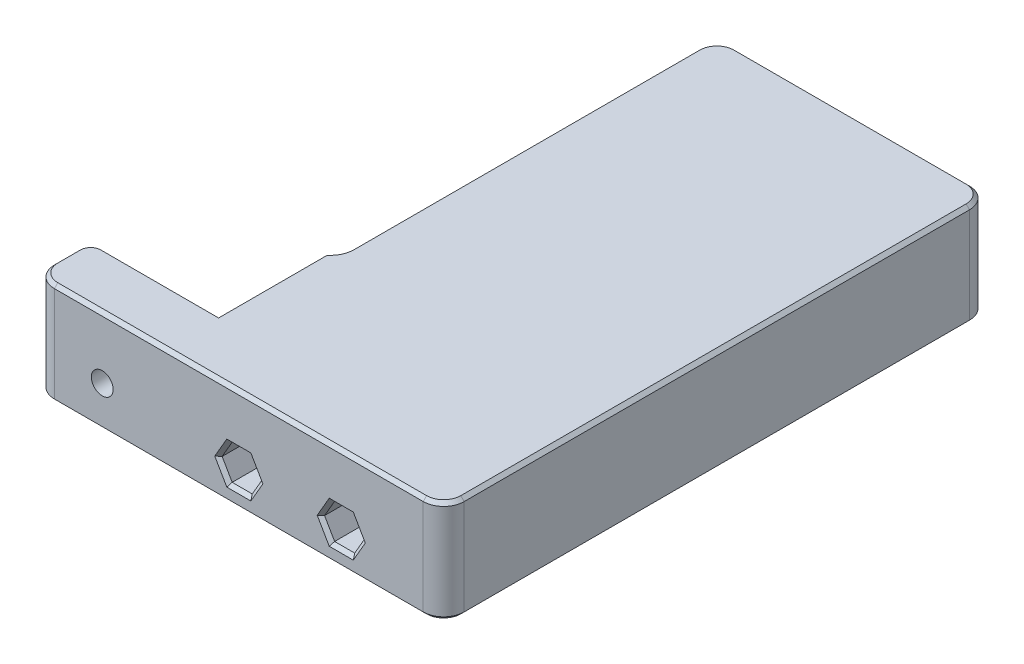
SolidWorks part; units mm, degrees
ref_plane "Front Plane" through (0, 0, 0) normal (0, 0, 1) x (1, 0, 0)
ref_plane "Top Plane" through (0, 0, 0) normal (0, 1, 0) x (1, 0, 0)
ref_plane "Right Plane" through (0, 0, 0) normal (1, 0, 0) x (0, 0, -1)
sketch "Sketch1" plane through (0, 0, 0) normal (0, 1, 0) x (1, 0, 0)
  line L1 (-38.1, -50.8) -> (38.1, -50.8)
  line L2 (-38.1, -50.8) -> (-38.1, 50.8)
  line L3 (-38.1, 50.8) -> (38.1, 50.8)
  line L4 (38.1, -50.8) -> (38.1, 50.8)
  line L5 (-38.1, -50.8) -> (38.1, 50.8) construction
  line L6 (-38.1, 50.8) -> (38.1, -50.8) construction
  point P0 (0, 0)
  dimension "D1" = 76.2
  dimension "D2" = 101.6
extrude "Boss-Extrude1" add sketch "Sketch1" along normal blind 19.05 contours L2 L3 L4 L1
sketch "Sketch2" plane through (0, 0, -50.8) normal (0, 0, -1) x (-1, 0, 0)
  line L0 (-38.1, 6.35) -> (38.1, 6.35) construction
  line L1 (-38.1, 19.05) -> (-38.1, 0) construction
  line L2 (38.1, 19.05) -> (38.1, 0) construction
  line L4 (-15.3105, 6.35) -> (-17.1803, 9.5885)
  line L5 (-17.1803, 9.5885) -> (-20.9197, 9.5885)
  line L6 (-20.9197, 9.5885) -> (-22.7895, 6.35)
  line L7 (-22.7895, 6.35) -> (-20.9197, 3.1115)
  line L8 (-20.9197, 3.1115) -> (-17.1803, 3.1115)
  line L9 (-17.1803, 3.1115) -> (-15.3105, 6.35)
  line L10 (3.7395, 6.35) -> (1.8697, 9.5885)
  line L11 (1.8697, 9.5885) -> (-1.8697, 9.5885)
  line L12 (-1.8697, 9.5885) -> (-3.7395, 6.35)
  line L13 (-3.7395, 6.35) -> (-1.8697, 3.1115)
  line L14 (-1.8697, 3.1115) -> (1.8697, 3.1115)
  line L15 (1.8697, 3.1115) -> (3.7395, 6.35)
  circle A0 centre (-19.05, 6.35) radius 3.2385 construction
  circle A1 centre (0, 6.35) radius 3.2385 construction
  point P16 (0, 0)
  point P24 (-8.9605, 8.89)
  point P25 (8.9605, 8.89)
  dimension "D1" = 6.35
  dimension "D2" = 6.477
  dimension "D3" = 6.477
  dimension "D4" = 19.05
  dimension "D5" = 19.05
extrude "Cut-Extrude1" cut sketch "Sketch2" against normal up to next contours L8 L9 L4 L5 L6 L7 | L14 L15 L10 L11 L12 L13
sketch "Sketch3" plane through (0, 0, 0) normal (0, -1, 0) x (1, 0, 0)
  line L0 (-38.1, 25.4) -> (38.1, 25.4) construction
  line L1 (-38.1, 50.8) -> (-38.1, -50.8) construction
  line L2 (38.1, 50.8) -> (38.1, -50.8) construction
  line L3 (-38.1, 0) -> (38.1, 0) construction
  line L4 (-38.1, 40.64) -> (-12.7, 19.05)
  line L5 (-12.7, 19.05) -> (-12.7, 0)
  line L6 (-12.7, 0) -> (-12.7, -50.8)
  line L7 (38.1, -50.8) -> (-38.1, -50.8) construction
  circle A0 centre (-6.35, 25.4) radius 2.032
  circle A1 centre (25.4, 25.4) radius 2.032
  circle A4 centre (25.4, -25.4) radius 2.032
  circle A5 centre (-6.35, -25.4) radius 2.032
  point P19 (-21.0605, -51.0911)
  point P21 (-12.7, 0)
  dimension "D1" = 4.064
  dimension "D3" = 31.75
  dimension "D2" = 31.75
  dimension "D4" = 25.4
  dimension "D5" = 10.16
  dimension "D6" = 25.4
  dimension "D7" = 19.05
  dimension "D8" = 25.4
extrude "Cut-Extrude2" cut sketch "Sketch3" against normal blind 9.525 contours A0 | A1 | A5 | A4
extrude "Cut-Extrude3" cut sketch "Sketch3<3>" against normal through all and the other way through all
sketch "Sketch3<3>" plane through (0, 0, 0) normal (0, -1, 0) x (1, 0, 0) same geometry as "Sketch3"
fillet "Fillet1" radius 3.81 6 edges at (38.1, 9.525, -50.8) (38.1, 9.525, 50.8) (-38.1, 9.525, 50.8) (-12.7, 9.525, -50.8) (-38.1, 9.525, 40.64) (-12.7, 9.525, 19.05)
chamfer "Chamfer1" distance 0.635 angle 45 52 edges at (0, 3.1115, -50.8) (-2.8046, 4.7308, -50.8) (-2.8046, 7.9692, -50.8) (0, 9.5885, -50.8) (2.8046, 7.9692, -50.8) (2.8046, 4.7308, -50.8) (19.05, 3.1115, -50.8) (16.2454, 4.7307, -50.8) (16.2454, 7.9693, -50.8) (19.05, 9.5885, -50.8) (21.8546, 7.9693, -50.8) (21.8546, 4.7307, -50.8) (0, 9.5885, 50.8) (-2.8046, 7.9692, 50.8) (-2.8046, 4.7308, 50.8) (0, 3.1115, 50.8) (2.8046, 4.7308, 50.8) (2.8046, 7.9692, 50.8) (19.05, 9.5885, 50.8) (16.2454, 7.9693, 50.8) (16.2454, 4.7307, 50.8) (19.05, 3.1115, 50.8) (21.8546, 4.7307, 50.8) (21.8546, 7.9693, 50.8) (-6.35, 0, -23.368) (25.4, 0, -23.368) (-6.35, 0, 23.368) (25.4, 0, 23.368) (38.1, 0, 0) (12.7, 0, -50.8) (0, 0, 50.8) (12.7, 19.05, -50.8) (38.1, 19.05, 0) (0, 19.05, 50.8) (-25.4, 0, 29.845) (-25.4, 19.05, 29.845) (-36.9841, 0, 49.6841) (36.9841, 0, 49.6841) (36.9841, 0, -49.6841) (-38.1, 0, 44.6959) (36.9841, 19.05, -49.6841) (36.9841, 19.05, 49.6841) (-36.9841, 19.05, 49.6841) (-38.1, 19.05, 44.6959) (-12.7, 19.05, -14.8509) (-12.7, 0, -14.8509) (-11.5841, 19.05, -49.6841) (-11.5841, 0, -49.6841) (-13.0519, 19.05, 18.8873) (-37.7481, 19.05, 40.8027) (-13.0519, 0, 18.8873) (-37.7481, 0, 40.8027)
sketch "Sketch5" plane through (0, 0, 50.8) normal (0, 0, 1) x (1, 0, 0)
  line L0 (-25.4591, 3.1754) -> (-38.1, 3.1754)
  line L1 (-21.5505, 5.3975) -> (-13.6682, 19.05)
  line L2 (-28.8006, 20.7631) -> (-29.8306, 7.9769)
  line L3 (-20.9614, 7.859) -> (-21.6512, 20.668)
  line L4 (-28.8006, 20.7631) -> (-29.8306, 7.9769)
  line L5 (-20.9614, 7.859) -> (-21.6512, 20.668)
  line L6 (-34.29, 0.635) -> (-34.29, 18.415) construction
  line L7 (-34.29, 18.415) -> (-38.1, 18.415) construction
  line L8 (-38.1, 18.415) -> (-38.1, 0.635) construction
  line L9 (-38.1, 0.635) -> (-34.29, 0.635) construction
  line L10 (34.29, 18.415) -> (34.29, 19.05) construction
  line L11 (34.29, 19.05) -> (-34.29, 19.05) construction
  line L12 (-34.29, 19.05) -> (-34.29, 18.415) construction
  line L13 (-34.29, 18.415) -> (34.29, 18.415) construction
  line L14 (-34.29, 0.635) -> (-34.29, 18.415)
  line L15 (-34.29, 18.415) -> (-38.1, 18.415)
  line L16 (-38.1, 18.415) -> (-38.1, 0.635)
  line L17 (-38.1, 0.635) -> (-34.29, 0.635)
  line L18 (34.29, 18.415) -> (34.29, 19.05)
  line L19 (34.29, 19.05) -> (-34.29, 19.05)
  line L20 (-34.29, 19.05) -> (-34.29, 18.415)
  line L21 (-34.29, 18.415) -> (34.29, 18.415)
  circle A1 centre (-25.4, 7.62) radius 2.032
  circle A2 centre (-25.4, 7.62) radius 2.032
  circle A3 centre (-24.7246, 58.4155) radius 2.032
  circle A4 centre (-24.7246, 58.4155) radius 2.032
  arc A10 (-21.743, 22.5616) -> (-21.6512, 20.668) centre (155.8916, 30.2285) ccw
  arc A11 (-16.1366, 56.1183) -> (-21.743, 22.5616) centre (155.625, 10.1747) ccw
  arc A12 (-16.1366, 56.1183) -> (-33.3707, 56.3475) centre (-24.7246, 58.4155) ccw
  arc A13 (-28.6584, 22.6536) -> (-33.3707, 56.3475) centre (-206.2931, 14.9866) ccw
  arc A14 (-28.8006, 20.7631) -> (-28.6584, 22.6536) centre (-206.0264, 35.0405) ccw
  arc A15 (-29.8306, 7.9769) -> (-20.9614, 7.859) centre (-25.4, 7.62) ccw
  arc A16 (-21.743, 22.5616) -> (-21.6512, 20.668) centre (155.8916, 30.2285) ccw
  arc A17 (-16.1366, 56.1183) -> (-21.743, 22.5616) centre (155.625, 10.1747) ccw
  arc A18 (-16.1366, 56.1183) -> (-33.3707, 56.3475) centre (-24.7246, 58.4155) ccw
  arc A19 (-28.6584, 22.6536) -> (-33.3707, 56.3475) centre (-206.2931, 14.9866) ccw
  arc A20 (-28.8006, 20.7631) -> (-28.6584, 22.6536) centre (-206.0264, 35.0405) ccw
  arc A21 (-29.8306, 7.9769) -> (-20.9614, 7.859) centre (-25.4, 7.62) ccw
  point P30 (-12.3207, 19.05)
  point P32 (-38.1, 3.1754)
  dimension "D4" = 60
  dimension "D1" = 0
  dimension "D2" = 0
  dimension "D3" = 0
extrude "Cut-Extrude4" cut sketch "Sketch5" against normal up to next contours A2
ref_plane "Plane1" through (0, 0, 40.259) normal (0, 0, 1) x (1, 0, 0)
sketch "Sketch6" plane through (0, 0, 40.259) normal (0, 0, 1) x (1, 0, 0)
  line L0 (-21.5505, 5.3975) -> (-13.6682, 19.05) construction
  line L1 (-25.4591, 3.1754) -> (-38.1, 3.1754) construction
  line L2 (-21.5505, 5.3975) -> (-13.6682, 19.05)
  line L3 (-25.4591, 3.1754) -> (-38.1, 3.1754)
  line L4 (-13.6682, 19.05) -> (-38.1, 19.05)
  line L5 (-38.1, 19.05) -> (-38.1, 3.1754)
  circle A0 centre (-25.4, 7.62) radius 2.032 construction
  arc A1 (-29.8306, 7.9769) -> (-20.9614, 7.859) centre (-25.4, 7.62) ccw construction
  circle A2 centre (-25.4, 7.62) radius 2.032
  arc A3 (-29.8306, 7.9769) -> (-20.9614, 7.859) centre (-25.4, 7.62) ccw
extrude "Cut-Extrude5" cut sketch "Sketch6" against normal through all contours L3 A3 L2 L4 L5 A2 region at (-28.1283, 11.9288, 40.259)
fillet "Fillet3" radius 2.54 1 edges at (-37.4403, 10.7952, 40.259)
chamfer "Chamfer3" distance 0.635 angle 45 2 edges at (-36.2882, 19.05, 40.3656) (-24.6141, 19.05, 40.259)
